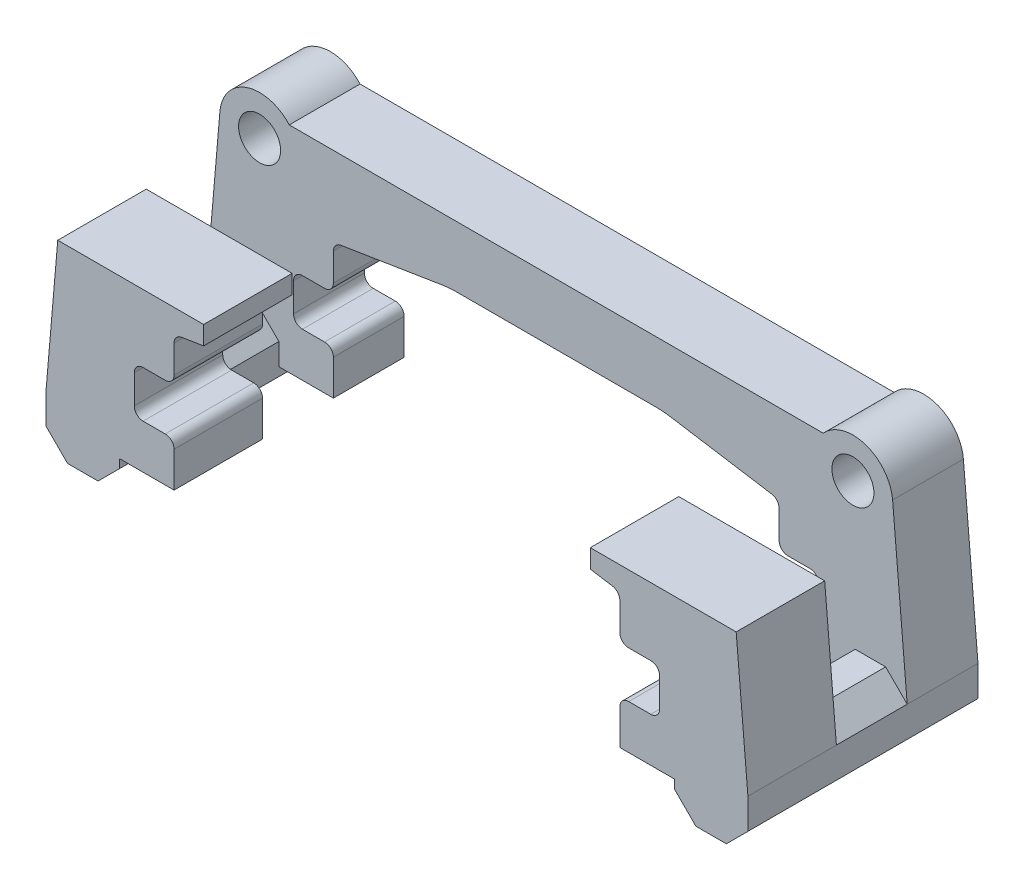
SolidWorks part; units mm, degrees
ref_plane "Front Plane" through (0, 0, 0) normal (0, 0, 1) x (1, 0, 0)
ref_plane "Top Plane" through (0, 0, 0) normal (0, 1, 0) x (1, 0, 0)
ref_plane "Right Plane" through (0, 0, 0) normal (1, 0, 0) x (0, 0, -1)
sketch "Sketch1" plane through (0, 0, 0) normal (0, 0, 1) x (1, 0, 0)
  line L0 (-79.3149, 0) -> (79.3149, 0) construction
  line L1 (0, 92.9069) -> (0, -13.0142) construction
  line L10 (-79.3149, 3.4442) -> (-76.014, 41.7722)
  line L11 (-62.6851, -3.4442) -> (-62.6851, 3.4442) construction
  line L12 (-62.6851, 3.4442) -> (-67.5558, 8.3149) construction
  line L13 (-67.5558, 8.3149) -> (-74.4442, 8.3149) construction
  line L14 (-74.4442, 8.3149) -> (-79.3149, 3.4442) construction
  line L15 (-79.3149, 3.4442) -> (-79.3149, -3.4442)
  line L16 (-79.3149, -3.4442) -> (-74.4442, -8.3149)
  line L17 (-74.4442, -8.3149) -> (-67.5558, -8.3149)
  line L18 (-67.5558, -8.3149) -> (-62.6851, -3.4442)
  line L19 (-75.3054, 50) -> (0, 50) construction
  line L20 (-79.3149, 3.4442) -> (-75.3054, 50) construction
  line L21 (-60.339, 47) -> (60.339, 47)
  line L22 (-72.5526, 47) -> (0, 47) construction
  line L23 (-76.326, 3.1867) -> (-72.5526, 47) construction
  line L24 (-62.6851, 0) -> (62.6851, 0) construction
  line L25 (75.3054, 50) -> (0, 50) construction
  line L26 (67.5558, -8.3149) -> (62.6851, -3.4442)
  line L27 (74.4442, -8.3149) -> (67.5558, -8.3149)
  line L28 (79.3149, -3.4442) -> (74.4442, -8.3149)
  line L29 (79.3149, 3.4442) -> (79.3149, -3.4442)
  line L30 (74.4442, 8.3149) -> (79.3149, 3.4442) construction
  line L31 (67.5558, 8.3149) -> (74.4442, 8.3149) construction
  line L32 (62.6851, 3.4442) -> (67.5558, 8.3149) construction
  line L33 (62.6851, -3.4442) -> (62.6851, 3.4442) construction
  line L34 (79.3149, 3.4442) -> (76.014, 41.7722)
  line L35 (-62.6851, -1.5) -> (62.6851, -1.5)
  line L36 (-62.6851, -1.5) -> (-62.6851, -3.4442)
  line L37 (62.6851, -1.5) -> (62.6851, -3.4442)
  circle A0 centre (-71, 0) radius 9 construction
  circle A2 centre (-71, 0) radius 5.115
  arc A3 (-60.339, 47) -> (-76.014, 41.7722) centre (-67.0472, 41) ccw
  circle A4 centre (-67.0472, 41) radius 4.75
  circle A5 centre (71, 0) radius 9 construction
  circle A6 centre (67.0472, 41) radius 4.75
  arc A7 (60.339, 47) -> (76.014, 41.7722) centre (67.0472, 41) cw
  circle A8 centre (71, 0) radius 5.115
  point P2 (0, 0)
  point P4 (-79.3149, 0)
  point P18 (0, 50)
  point P39 (0, 0)
  dimension "D2" = 18
  dimension "D3" = 10.23
  dimension "D4" = 50
  dimension "D5" = 18
  dimension "D6" = 9.5
  dimension "D1" = 142
  dimension "D7" = 3
  dimension "D8" = 1.5
extrude "Boss-Extrude1" add sketch "Sketch1" along normal blind 16
sketch "Sketch2" plane through (0, 0, 0) normal (0, 0, -1) x (-1, 0, 0)
  line L0 (0, 55.269) -> (0, -24.0682) construction
  line L1 (-50.3702, 1.5) -> (-50.3702, 8.5) construction
  line L2 (0, 47) -> (0, -1.5)
  line L3 (62.6851, -1.5) -> (-62.6851, -1.5) construction
  line L4 (-60.339, 47) -> (60.339, 47) construction
  line L11 (-50.3702, 6.5) -> (-50.3702, -1.5)
  line L14 (-52.3702, 8.5) -> (-57.3702, 8.5)
  line L22 (-52.3702, 19) -> (-57.3702, 19)
  line L23 (-59.3702, 10.5) -> (-59.3702, 17)
  line L24 (-50.3702, 21) -> (-50.3702, 27.2956)
  line L25 (-50.3702, 32.7118) -> (54.6448, 32.7118) construction
  line L26 (-22.5495, 33.2118) -> (22.5495, 33.2118)
  line L27 (-48.6873, 29.2703) -> (-25.7209, 32.9587)
  line L28 (48.6873, 29.2703) -> (25.7209, 32.9587)
  line L29 (50.3702, 21) -> (50.3702, 27.2956)
  line L30 (59.3702, 10.5) -> (59.3702, 17)
  line L31 (52.3702, 19) -> (57.3702, 19)
  line L32 (52.3702, 8.5) -> (57.3702, 8.5)
  line L33 (50.3702, 6.5) -> (50.3702, -1.5)
  line L34 (-50.3702, 19) -> (-50.3702, 50) construction
  line L35 (-59.3702, 13.75) -> (59.3702, 13.75) construction
  line L36 (50.3702, -1.5) -> (25.7209, -5.4587)
  line L37 (-50.3702, -1.5) -> (-25.7209, -5.4587)
  line L38 (-22.5495, -5.7118) -> (22.5495, -5.7118)
  line L39 (-48.3702, 6.5) -> (-48.3702, 0.2044)
  line L40 (-48.3702, 0.2044) -> (-25.4037, -3.484)
  line L41 (-22.5495, -3.7118) -> (22.5495, -3.7118)
  line L42 (48.3702, 0.2044) -> (25.4037, -3.484)
  line L43 (48.3702, 6.5) -> (48.3702, 0.2044)
  line L44 (52.3702, 10.5) -> (57.3702, 10.5)
  line L45 (57.3702, 10.5) -> (57.3702, 17)
  line L46 (52.3702, 17) -> (57.3702, 17)
  line L47 (48.3702, 21) -> (48.3702, 27.2956)
  line L48 (48.3702, 27.2956) -> (25.4037, 30.984)
  line L49 (-22.5495, 31.2118) -> (22.5495, 31.2118)
  line L50 (-48.3702, 27.2956) -> (-25.4037, 30.984)
  line L51 (-48.3702, 21) -> (-48.3702, 27.2956)
  line L52 (-52.3702, 17) -> (-57.3702, 17)
  line L53 (-57.3702, 10.5) -> (-57.3702, 17)
  line L54 (-52.3702, 10.5) -> (-57.3702, 10.5)
  line L55 (-28.2818, 22.75) -> (28.2818, 22.75) construction
  line L56 (0, 15.6004) -> (-5.8172, 15.6004) construction
  line L57 (-3.0332, 15.6004) -> (3.0332, 15.6004) construction
  circle A15 centre (0, 3) radius 32.8 construction
  arc A17 (25.7209, 32.9587) -> (22.5495, 33.2118) centre (22.5495, 13.2118) ccw
  arc A18 (-25.7209, 32.9587) -> (-22.5495, 33.2118) centre (-22.5495, 13.2118) cw
  arc A19 (59.3702, 17) -> (57.3702, 19) centre (57.3702, 17) ccw
  arc A20 (59.3702, 10.5) -> (57.3702, 8.5) centre (57.3702, 10.5) cw
  arc A21 (50.3702, 6.5) -> (52.3702, 8.5) centre (52.3702, 6.5) cw
  arc A22 (50.3702, 21) -> (52.3702, 19) centre (52.3702, 21) ccw
  arc A23 (48.6873, 29.2703) -> (50.3702, 27.2956) centre (48.3702, 27.2956) cw
  arc A24 (-50.3702, 27.2956) -> (-48.6873, 29.2703) centre (-48.3702, 27.2956) cw
  arc A25 (-52.3702, 8.5) -> (-50.3702, 6.5) centre (-52.3702, 6.5) cw
  arc A26 (-50.3702, 21) -> (-52.3702, 19) centre (-52.3702, 21) cw
  arc A27 (-57.3702, 19) -> (-59.3702, 17) centre (-57.3702, 17) ccw
  arc A28 (-57.3702, 8.5) -> (-59.3702, 10.5) centre (-57.3702, 10.5) cw
  arc A29 (25.7209, -5.4587) -> (22.5495, -5.7118) centre (22.5495, 14.2882) cw
  arc A30 (-25.7209, -5.4587) -> (-22.5495, -5.7118) centre (-22.5495, 14.2882) ccw
  arc A31 (-25.4037, -3.484) -> (-22.5495, -3.7118) centre (-22.5495, 14.2882) ccw
  arc A32 (25.4037, -3.484) -> (22.5495, -3.7118) centre (22.5495, 14.2882) cw
  arc A33 (48.3702, 6.5) -> (52.3702, 10.5) centre (52.3702, 6.5) cw
  arc A34 (48.3702, 21) -> (52.3702, 17) centre (52.3702, 21) ccw
  arc A35 (25.4037, 30.984) -> (22.5495, 31.2118) centre (22.5495, 13.2118) ccw
  arc A36 (-25.4037, 30.984) -> (-22.5495, 31.2118) centre (-22.5495, 13.2118) cw
  arc A37 (-48.3702, 21) -> (-52.3702, 17) centre (-52.3702, 21) cw
  arc A38 (-52.3702, 10.5) -> (-48.3702, 6.5) centre (-52.3702, 6.5) cw
  point P19 (0, 33.2118)
  point P73 (57.3702, 13.75)
  point P75 (0, -3.7118)
  point P93 (0, 31.2118)
  point P102 (-57.3702, 13.75)
  point P106 (-8.715, 22.75)
  point P111 (0, 15.6004)
  dimension "D1" = 65.6
  dimension "D2" = 20
  dimension "D3" = 8
  dimension "D4" = 6.5
extrude "Cut-Extrude1" cut sketch "Sketch2" against normal through all contours L27 A18 L26 A17 L28 A23 L29 A22 L31 A19 L30 A20 L32 A21 L33 L36 A29 L38 A30 L37 L11 A25 L14 A28 L23 A27 L22 A26 L24 A24
sketch "Sketch3" plane through (0, 0, 16) normal (0, 0, 1) x (1, 0, 0)
  line L0 (-79.3149, 3.4442) -> (-79.3149, -3.4442) construction
  line L1 (-79.3149, -3.4442) -> (-74.4442, -8.3149) construction
  line L2 (-74.4442, -8.3149) -> (-67.5558, -8.3149) construction
  line L3 (-67.5558, -8.3149) -> (-62.6851, -3.4442) construction
  line L4 (-62.6851, -3.4442) -> (-62.6851, 3.4442) construction
  line L5 (-62.6851, 3.4442) -> (-67.5558, 8.3149) construction
  line L6 (-67.5558, 8.3149) -> (-74.4442, 8.3149) construction
  line L7 (-74.4442, 8.3149) -> (-79.3149, 3.4442) construction
  line L8 (-79.3149, 3.4442) -> (-79.3149, -3.4442)
  line L9 (-79.3149, -3.4442) -> (-74.4442, -8.3149)
  line L10 (-74.4442, -8.3149) -> (-67.5558, -8.3149)
  line L11 (-67.5558, -8.3149) -> (-62.6851, -3.4442)
  line L12 (-62.6851, -3.4442) -> (-62.6851, 3.4442)
  line L13 (-62.6851, 3.4442) -> (-67.5558, 8.3149)
  line L14 (-67.5558, 8.3149) -> (-74.4442, 8.3149)
  line L15 (-74.4442, 8.3149) -> (-79.3149, 3.4442)
  circle A0 centre (-71, 0) radius 9 construction
  circle A1 centre (-71, 0) radius 9 construction
  circle A2 centre (-71, 0) radius 5.115 construction
  circle A3 centre (-71, 0) radius 5.115
extrude "Boss-Extrude2" add sketch "Sketch3" along normal blind 16
mirror "Mirror1" about plane through (0, 0, 0) normal (1, 0, 0) of "Boss-Extrude2"
ref_plane "Plane1" through (0, 0, 32) normal (0, 0, 1) x (1, 0, 0)
sketch "Sketch4" plane through (0, 0, 32) normal (0, 0, 1) x (1, 0, 0)
  line L2 (-50.3702, 27.2956) -> (-84.694, 27.2956) construction
  line L4 (-50.3702, 6.5) -> (-50.3702, -1.5) construction
  line L5 (-52.3702, 8.5) -> (-57.3702, 8.5) construction
  line L6 (-59.3702, 10.5) -> (-59.3702, 17) construction
  line L7 (-52.3702, 19) -> (-57.3702, 19) construction
  line L8 (-50.3702, 21) -> (-50.3702, 27.2956) construction
  line L9 (-50.3702, 6.5) -> (-50.3702, -1.5)
  line L10 (-52.3702, 8.5) -> (-57.3702, 8.5)
  line L11 (-59.3702, 10.5) -> (-59.3702, 17)
  line L12 (-52.3702, 19) -> (-57.3702, 19)
  line L13 (-50.3702, 21) -> (-50.3702, 27.2956)
  line L14 (-43.6873, 34.2703) -> (-76.6601, 34.2703)
  line L16 (-48.6873, 29.2703) -> (-48.6873, 34.2703) construction
  line L18 (-48.6873, 29.2703) -> (-25.7209, 32.9587) construction
  line L19 (-48.6873, 29.2703) -> (-43.6873, 30.0733)
  line L20 (-43.6873, 34.2703) -> (-43.6873, 30.0733)
  line L42 (-62.6851, -1.5) -> (62.6851, -1.5)
  line L43 (-62.6851, -3.4442) -> (-62.6851, -1.5)
  line L44 (-67.5558, -8.3149) -> (-62.6851, -3.4442)
  line L45 (-74.4442, -8.3149) -> (-67.5558, -8.3149)
  line L46 (-79.3149, -3.4442) -> (-74.4442, -8.3149)
  line L47 (-79.3149, 3.4442) -> (-79.3149, -3.4442)
  line L48 (-76.014, 41.7722) -> (-79.3149, 3.4442)
  line L49 (60.339, 47) -> (-60.339, 47)
  line L50 (79.3149, 3.4442) -> (76.014, 41.7722)
  line L51 (79.3149, -3.4442) -> (79.3149, 3.4442)
  line L52 (74.4442, -8.3149) -> (79.3149, -3.4442)
  line L53 (67.5558, -8.3149) -> (74.4442, -8.3149)
  line L54 (62.6851, -3.4442) -> (67.5558, -8.3149)
  line L55 (62.6851, -1.5) -> (62.6851, -3.4442)
  line L56 (-62.6851, -1.5) -> (-50.3702, -1.5)
  line L57 (-62.6851, -3.4442) -> (-62.6851, -1.5)
  line L58 (-67.5558, -8.3149) -> (-62.6851, -3.4442)
  line L59 (-74.4442, -8.3149) -> (-67.5558, -8.3149)
  line L60 (-79.3149, -3.4442) -> (-74.4442, -8.3149)
  line L61 (-79.3149, 3.4442) -> (-79.3149, -3.4442)
  line L62 (-76.6601, 34.2703) -> (-79.3149, 3.4442)
  arc A0 (-50.3702, 6.5) -> (-52.3702, 8.5) centre (-52.3702, 6.5) ccw construction
  arc A1 (-59.3702, 10.5) -> (-57.3702, 8.5) centre (-57.3702, 10.5) ccw construction
  arc A3 (-57.3702, 19) -> (-59.3702, 17) centre (-57.3702, 17) ccw construction
  arc A5 (-52.3702, 19) -> (-50.3702, 21) centre (-52.3702, 21) ccw construction
  arc A7 (-50.3702, 6.5) -> (-52.3702, 8.5) centre (-52.3702, 6.5) ccw
  arc A9 (-59.3702, 10.5) -> (-57.3702, 8.5) centre (-57.3702, 10.5) ccw
  arc A10 (-60.339, 47) -> (-76.014, 41.7722) centre (-67.0472, 41) ccw
  arc A11 (76.014, 41.7722) -> (60.339, 47) centre (67.0472, 41) ccw
  arc A30 (-57.3702, 19) -> (-59.3702, 17) centre (-57.3702, 17) ccw
  arc A31 (-52.3702, 19) -> (-50.3702, 21) centre (-52.3702, 21) ccw
  arc A32 (-48.6873, 29.2703) -> (-50.3702, 27.2956) centre (-48.3702, 27.2956) ccw construction
  arc A33 (-48.6873, 29.2703) -> (-50.3702, 27.2956) centre (-48.3702, 27.2956) ccw
  dimension "D1" = 5
  dimension "D2" = 5
  dimension "D6" = 0
extrude "Boss-Extrude3" add sketch "Sketch4" along normal blind 20
mirror "Mirror2" about plane through (0, 0, 0) normal (1, 0, 0) of "Boss-Extrude3"
equation "\"disk_thickness\"=10"
equation "\"D1@Boss-Extrude1\"=16"
